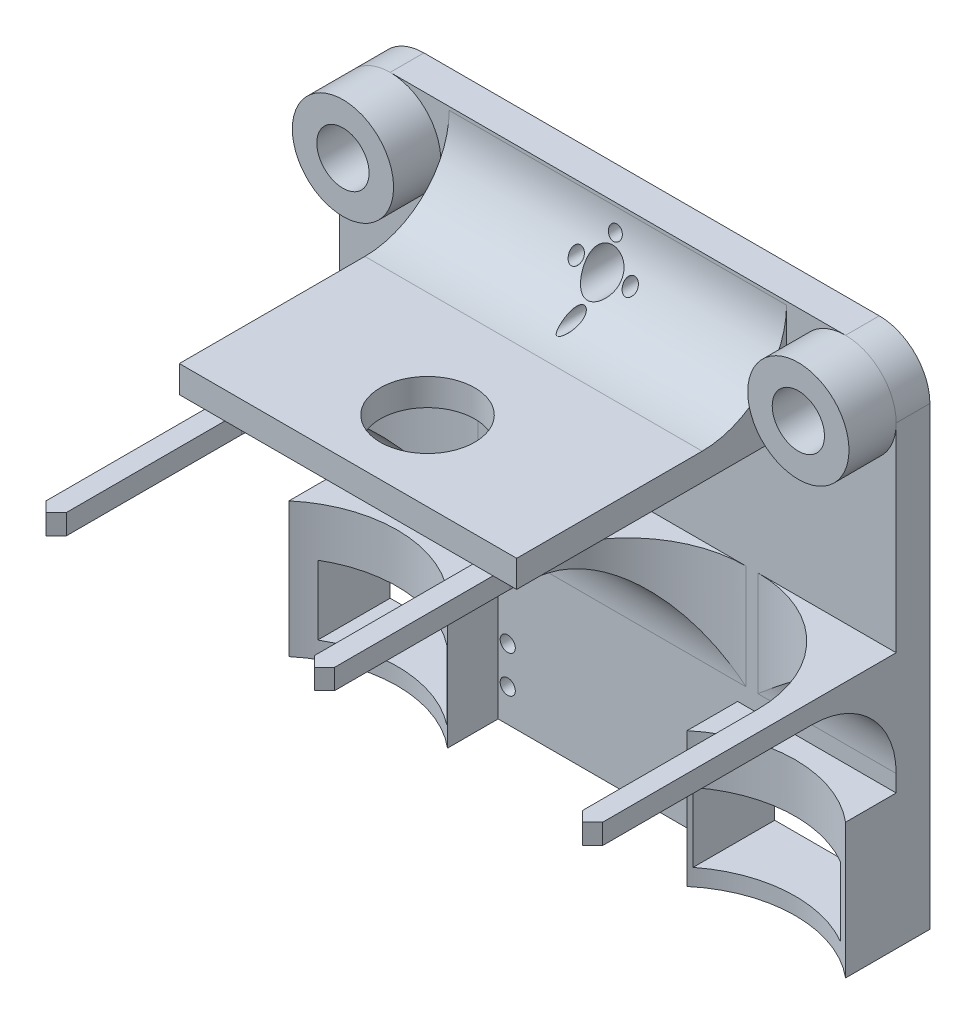
SolidWorks part; units mm, degrees
ref_plane "Plan de face" through (0, 0, 0) normal (0, 0, 1) x (1, 0, 0)
ref_plane "Plan de dessus" through (0, 0, 0) normal (0, 1, 0) x (1, 0, 0)
ref_plane "Plan de droite" through (0, 0, 0) normal (1, 0, 0) x (0, 0, -1)
sketch "Esquisse1" plane through (0, 0, 0) normal (0, 0, 1) x (1, 0, 0)
  line L1 (-82.5, -75) -> (82.5, -75)
  line L2 (-82.5, -75) -> (-82.5, 75)
  line L3 (-82.5, 75) -> (82.5, 75)
  line L4 (82.5, -75) -> (82.5, 75)
  line L5 (-82.5, -75) -> (82.5, 75) construction
  line L6 (-82.5, 75) -> (82.5, -75) construction
  point P0 (0, 0)
  dimension "D1" = 165
  dimension "D2" = 150
extrude "Boss.-Extru.1" add sketch "Esquisse1" along normal blind 10
sketch "Esquisse2" plane through (0, 0, 10) normal (0, 0, 1) x (1, 0, 0)
  line L0 (-82.5, 75) -> (-82.5, -75) construction
  line L1 (82.5, 75) -> (-82.5, 75) construction
  line L2 (0, -55) -> (0, 55) construction
  circle A0 centre (-67.5, 60) radius 7.75
  circle A2 centre (67.5, 60) radius 7.75
  dimension "D1" = 15.5
  dimension "D3" = 15
  dimension "D2" = 15
extrude "Enlèv. mat.-Extru.1" cut sketch "Esquisse2" against normal blind 10
sketch "Esquisse3" plane through (0, 0, 0) normal (0, 0, -1) x (-1, 0, 0)
  circle A0 centre (-67.5, 60) radius 15
  circle A1 centre (67.5, 60) radius 15
  circle A2 centre (-67.5, 60) radius 7.75
  circle A3 centre (67.5, 60) radius 7.75
  dimension "D1" = 30
  dimension "D2" = 30
extrude "Boss.-Extru.2" add sketch "Esquisse3" against normal blind 24
fillet "Congé1" radius 15 2 edges at (82.5, 75, 5) (-82.5, 75, 5)
sketch "Esquisse4" plane through (0, 0, 0) normal (0, 0, -1) x (-1, 0, 0)
  line L0 (-67.5, 75) -> (67.5, 75) construction
  circle A0 centre (0, 60) radius 5.25
  circle A1 centre (0, 60) radius 11
  circle A2 centre (0, 52) radius 2
  circle A3 centre (-8, 60) radius 2
  circle A4 centre (0, 68) radius 2
  circle A5 centre (8, 60) radius 2
  point P4 (0, 0)
  point P5 (0, 0)
  point P9 (0, 60)
  point P18 (0, 60)
  dimension "D1" = 10.5
  dimension "D2" = 15
  dimension "D4" = 22
  dimension "D5" = 4
  dimension "D6" = 8
  dimension "D7" = 4
extrude "Enlèv. mat.-Extru.2" cut sketch "Esquisse4" against normal blind 28 contours A2 | A5 | A4 | A3 | A0
sketch "Esquisse6" plane through (0, -75, 0) normal (0, -1, 0) x (1, 0, 0)
  line L0 (-82.5, 10) -> (82.5, 10) construction
  line L1 (-82.5, 25) -> (-82.5, 10)
  line L2 (-82.5, 10) -> (-35.5, 10)
  line L3 (-35.5, 10) -> (-35.5, 25)
  line L4 (0, 0) -> (0, 41.8553) construction
  line L5 (35.5, 10) -> (35.5, 25)
  line L6 (82.5, 10) -> (35.5, 10)
  line L7 (82.5, 25) -> (82.5, 10)
  arc A0 (-82.5, 25) -> (-35.5, 25) centre (-59, 52.9285) ccw
  arc A1 (82.5, 25) -> (35.5, 25) centre (59, 52.9285) cw
  dimension "D1" = 36.5
  dimension "D2" = 47
  dimension "D3" = 15
extrude "Boss.-Extru.3" add sketch "Esquisse6" against normal blind 40
sketch "Esquisse5" plane through (0, 0, 0) normal (0, 0, -1) x (-1, 0, 0)
  line L0 (-82.5, -75) -> (-82.5, 60) construction
  line L1 (-77.5, -70) -> (-36.5, -70)
  line L2 (-77.5, -70) -> (-77.5, -49.5)
  line L3 (-77.5, -49.5) -> (-36.5, -49.5)
  line L4 (-36.5, -70) -> (-36.5, -49.5)
  line L5 (82.5, -75) -> (-82.5, -75) construction
  line L6 (0, 5.5) -> (0, -5.5) construction
  line L7 (36.5, -70) -> (36.5, -49.5)
  line L8 (77.5, -70) -> (36.5, -70)
  line L9 (77.5, -70) -> (77.5, -49.5)
  line L10 (77.5, -49.5) -> (36.5, -49.5)
  line L11 (-77.5, -59.75) -> (-36.5, -59.75) construction
  circle A0 centre (-32.65, -54.25) radius 2.25
  circle A2 centre (-32.65, -65.25) radius 2.25
  circle A3 centre (32.65, -65.25) radius 2.25
  circle A4 centre (32.65, -54.25) radius 2.25
  dimension "D5" = 4.5
  dimension "D6" = 4.75
  dimension "D1" = 41
  dimension "D2" = 20.5
  dimension "D3" = 5
  dimension "D4" = 5
  dimension "D8" = 3.85
extrude "Enlèv. mat.-Extru.3" cut sketch "Esquisse5" against normal blind 30
sketch "Esquisse8" plane through (0, 0, 10) normal (0, 0, 1) x (1, 0, 0)
  line L0 (67.5, 75) -> (-67.5, 75) construction
  line L1 (-50, 41) -> (50, 41)
  line L2 (-50, 41) -> (-50, 49)
  line L3 (-50, 49) -> (50, 49)
  line L4 (50, 41) -> (50, 49)
  line L5 (-50, 41) -> (50, 49) construction
  line L6 (-50, 49) -> (50, 41) construction
  point P0 (0, 45)
  point P5 (0, 22.676)
  point P8 (26.6837, 21)
  point P9 (0, 0)
  dimension "D1" = 8
  dimension "D2" = 100
  dimension "D3" = 30
extrude "Boss.-Extru.4" add sketch "Esquisse8" along normal blind 80
sketch "Esquisse9" plane through (0, 0, 10) normal (0, 0, 1) x (1, 0, 0)
  line L0 (-82.5, 60) -> (-82.5, -35) construction
  line L1 (-82.5, -5) -> (-76.5, -5)
  line L2 (-82.5, -5) -> (-82.5, 1)
  line L3 (-82.5, 1) -> (-76.5, 1)
  line L4 (-76.5, -5) -> (-76.5, 1)
  line L5 (-82.5, -5) -> (-76.5, 1) construction
  line L6 (-82.5, 1) -> (-76.5, -5) construction
  line L7 (-50, 41) -> (50, 41) construction
  line L8 (0, 25.5214) -> (0, 7.1933) construction
  line L9 (82.5, 1) -> (76.5, -5) construction
  line L10 (82.5, -5) -> (76.5, 1) construction
  line L11 (76.5, -5) -> (76.5, 1)
  line L12 (82.5, 1) -> (76.5, 1)
  line L13 (82.5, -5) -> (82.5, 1)
  line L14 (82.5, -5) -> (76.5, -5)
  line L16 (3, 1) -> (-3, 1)
  line L17 (3, 1) -> (3, -5)
  line L18 (3, -5) -> (-3, -5)
  line L19 (-3, 1) -> (-3, -5)
  line L20 (3, 1) -> (-3, -5) construction
  line L21 (3, -5) -> (-3, 1) construction
  point P0 (-79.5, -2)
  point P16 (79.5, -2)
  point P22 (0, 0)
  point P23 (11.4058, -5)
  point P24 (0, -2)
  point P25 (0, 0)
  dimension "D1" = 6
  dimension "D2" = 6
  dimension "D3" = 0
  dimension "D4" = 40
  dimension "D5" = 6
  dimension "D6" = 6
extrude "Boss.-Extru.5" add sketch "Esquisse9" along normal blind 90
fillet "Congé2" radius 35 4 edges at (3, -2, 10) (-76.5, -2, 10) (76.5, -2, 10) (-3, -2, 10)
sketch "Esquisse10" plane through (0, 49, 0) normal (0, 1, 0) x (1, 0, 0)
  line L0 (-59, -52.9285) -> (63.4141, -52.9285) construction
  line L1 (0, -52.9285) -> (0, -16.4285) construction
  line L2 (0, -16.4285) -> (0, -66.4285) construction
  circle A1 centre (0, -66.4285) radius 14
  dimension "D3" = 28
  dimension "D1" = 36.5
  dimension "D2" = 50
extrude "Enlèv. mat.-Extru.5" cut sketch "Esquisse10" against normal blind 35
chamfer "Chanfrein1" distance 3 angle 45 6 edges at (76.5, -2, 100) (82.5, -2, 100) (-3, -2, 100) (3, -2, 100) (-82.5, -2, 100) (-76.5, -2, 100)
fillet "Congé3" radius 25 3 edges at (62, -5, 10) (0, -5, 10) (-62, -5, 10)
fillet "Congé4" radius 25 1 edges at (0, 49, 10)
